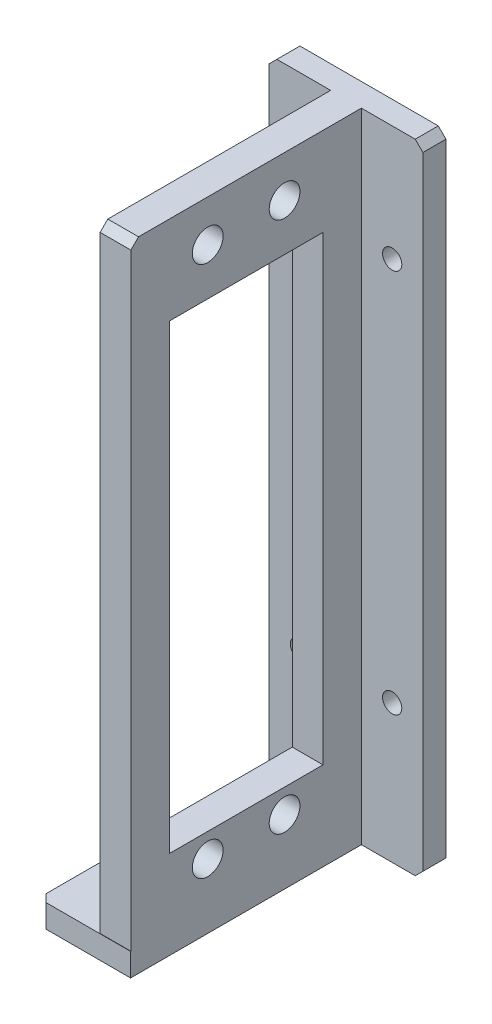
SolidWorks part; units mm, degrees
ref_plane "Alzado" through (0, 0, 0) normal (0, 0, 1) x (1, 0, 0)
ref_plane "Planta" through (0, 0, 0) normal (0, 1, 0) x (1, 0, 0)
ref_plane "Vista lateral" through (0, 0, 0) normal (1, 0, 0) x (0, 0, -1)
sketch "Croquis2" plane through (0, 0, 0) normal (0, 0, 1) x (1, 0, 0)
  line L1 (10, 40) -> (-10, 40)
  line L2 (10, 40) -> (10, -40)
  line L3 (10, -40) -> (-10, -40)
  line L4 (-10, 40) -> (-10, -40)
  line L5 (10, 40) -> (-10, -40) construction
  line L6 (10, -40) -> (-10, 40) construction
  point P0 (0, 0)
  dimension "D1" = 20
  dimension "D2" = 80
extrude "Saliente-Extruir2" add sketch "Croquis2" along normal blind 3
sketch "Croquis3" plane through (0, 0, 3) normal (0, 0, 1) x (1, 0, 0)
  line L0 (10, 40) -> (-10, 40) construction
  line L1 (-2, 40) -> (2, 40)
  line L2 (-2, 40) -> (-2, -40)
  line L3 (-2, -40) -> (2, -40)
  line L4 (2, 40) -> (2, -40)
  line L5 (-10, -40) -> (10, -40) construction
  line L6 (-2, 15.5368) -> (-10, 15.5368) construction
  line L7 (-10, 40) -> (-10, -40) construction
  line L8 (2, -3.0673) -> (10, -3.0673) construction
  line L9 (10, -40) -> (10, 40) construction
  dimension "D1" = 4
extrude "Saliente-Extruir3" add sketch "Croquis3" along normal blind 30
sketch "Croquis4" plane through (0, 0, 3) normal (0, 0, 1) x (1, 0, 0)
  line L0 (-10, 25) -> (10, 25) construction
  line L1 (-10, 40) -> (-10, -40) construction
  line L2 (10, -40) -> (10, 40) construction
  line L3 (-6, 25) -> (-6, 23.75) construction
  line L4 (-6, 25) -> (-6, 40) construction
  line L5 (2, 40) -> (-2, 40) construction
  line L6 (0, 40) -> (0, 0) construction
  line L7 (-2, 40) -> (-10, 40) construction
  line L8 (-6, -25) -> (-6, -40) construction
  line L9 (-10, -40) -> (-2, -40) construction
  line L10 (6, -25) -> (6, -40) construction
  line L11 (2, -40) -> (10, -40) construction
  line L12 (6, 25) -> (6, 23.75) construction
  line L13 (6, 25) -> (6, 40) construction
  line L14 (10, 40) -> (2, 40) construction
  line L15 (-6, -23.75) -> (-6, -25) construction
  line L16 (6, -23.75) -> (6, -25) construction
  circle A0 centre (-6, 25) radius 1.25
  circle A1 centre (6, 25) radius 1.25
  circle A2 centre (6, -25) radius 1.25
  circle A3 centre (-6, -25) radius 1.25
  point P10 (0, 0)
  dimension "D1" = 2.5
  dimension "D2" = 50
extrude "Cortar-Extruir1" cut sketch "Croquis4" against normal blind 23
sketch "Croquis6" plane through (0, -40, 0) normal (0, -1, 0) x (1, 0, 0)
  line L0 (2, 3) -> (2, 0) construction
  line L1 (-10, 0) -> (10, 0) construction
  line L3 (2, 0) -> (-10, 0)
  line L4 (2, 0) -> (2, 33.0374)
  line L5 (2, 33.0374) -> (-10, 33.0374)
  line L6 (-10, 0) -> (-10, 33.0374)
extrude "Saliente-Extruir4" add sketch "Croquis6" along normal blind 3
sketch "Croquis5" plane through (-2, 0, 0) normal (-1, 0, 0) x (0, 0, 1)
  line L0 (13, 34.6) -> (23, 34.6) construction
  line L1 (13, 34.6) -> (3, 34.6) construction
  line L2 (3, 40) -> (3, -40) construction
  line L3 (23, 34.6) -> (33, 34.6) construction
  line L4 (33, 40) -> (33, -40) construction
  line L5 (3, 0) -> (33, 0) construction
  line L6 (13, 34.6) -> (13, 30) construction
  line L7 (13, 30) -> (13, 0) construction
  circle A0 centre (13, 34.6) radius 2
  circle A1 centre (23, 34.6) radius 2
  circle A2 centre (23, -34.6) radius 2
  circle A3 centre (13, -34.6) radius 2
  dimension "D2" = 4
  dimension "D3" = 4
  dimension "D1" = 10
  dimension "D4" = 4.6
  dimension "D5" = 30
extrude "Cortar-Extruir2" cut sketch "Croquis5" against normal through all
chamfer "Chaflán1" distance 10 angle 45 1 edges at (2, -40, 1.5)
chamfer "Chaflán2" distance 1 angle 45 4 edges at (-10, -41.5, 33.0374) (0, 40, 33) (-10, 40, 1.5) (10, 40, 1.5)
sketch "Croquis7" plane through (2, 0, 0) normal (1, 0, 0) x (0, 0, -1)
  line L0 (-18, -1.5) -> (-3, -1.5) construction
  line L1 (-8, 28.5) -> (-28, 28.5)
  line L2 (-8, 28.5) -> (-8, -31.5)
  line L3 (-8, -31.5) -> (-28, -31.5)
  line L4 (-28, 28.5) -> (-28, -31.5)
  line L5 (-8, 28.5) -> (-28, -31.5) construction
  line L6 (-8, -31.5) -> (-28, 28.5) construction
  line L7 (-3, -42) -> (-3, 39) construction
  line L8 (-18, -1.5) -> (-18, 40) construction
  line L9 (-32, 40) -> (-3, 40) construction
  line L10 (-18, -1.5) -> (-33, -1.5) construction
  line L11 (-33, -40) -> (-33, 39) construction
  line L12 (-18, -1.5) -> (-18.0187, -43) construction
  line L13 (-3, -43) -> (-33.0374, -43) construction
  point P0 (-18, -1.5)
  dimension "D1" = 20
  dimension "D2" = 60
extrude "Cortar-Extruir3" cut sketch "Croquis7" against normal through all both and the other way through all
